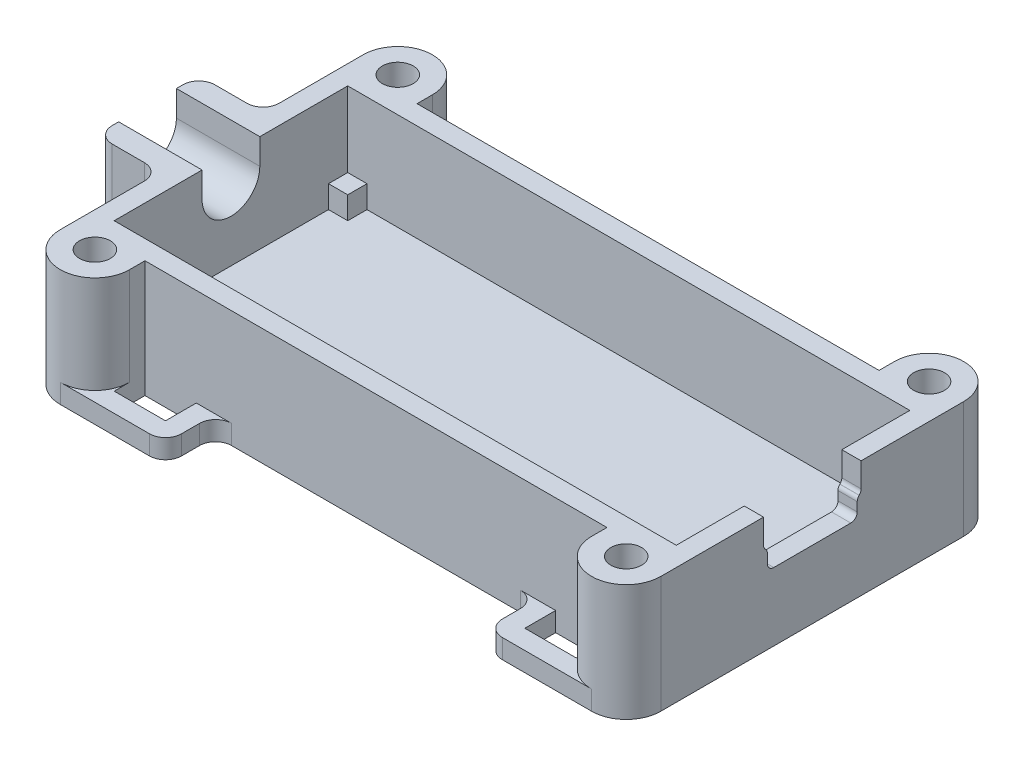
SolidWorks part; units mm, degrees
ref_plane "Front Plane" through (0, 0, 0) normal (0, 0, 1) x (1, 0, 0)
ref_plane "Top Plane" through (0, 0, 0) normal (0, 1, 0) x (1, 0, 0)
ref_plane "Right Plane" through (0, 0, 0) normal (1, 0, 0) x (0, 0, -1)
sketch "Sketch1" plane through (0, 0, 0) normal (0, 1, 0) x (1, 0, 0)
  line L0 (-21.9, 9.1) -> (-23.4, 9.1) construction
  line L1 (-21.9, 9.1) -> (21.9, 9.1)
  line L2 (-21.9, 9.1) -> (-21.9, -9.1)
  line L3 (-21.9, -9.1) -> (21.9, -9.1)
  line L4 (21.9, 9.1) -> (21.9, -9.1)
  line L5 (-21.9, 9.1) -> (21.9, -9.1) construction
  line L6 (-21.9, -9.1) -> (21.9, 9.1) construction
  line L7 (23.4, -10.6) -> (-23.4, -10.6)
  line L8 (23.4, -10.6) -> (23.4, 10.6)
  line L9 (23.4, 10.6) -> (-23.4, 10.6)
  line L10 (-23.4, -10.6) -> (-23.4, 10.6)
  line L11 (23.4, -10.6) -> (-23.4, 10.6) construction
  line L12 (23.4, 10.6) -> (-23.4, -10.6) construction
  line L13 (-21.9, 9.1) -> (-21.9, 10.6) construction
  line L14 (-19.5, 11.8) -> (-18, 11.8) construction
  line L15 (-23.4, 11.8) -> (-23.4, 10.6)
  line L16 (0, 30.5142) -> (0, -27.0472) construction
  line L17 (-40.1948, 0) -> (31.8876, 0) construction
  line L18 (-18, 11.8) -> (-18, 10.6)
  line L19 (18, 11.8) -> (18, 10.6)
  line L20 (23.4, 11.8) -> (23.4, 10.6)
  line L21 (23.4, -11.8) -> (23.4, -10.6)
  line L22 (18, -11.8) -> (18, -10.6)
  line L23 (-18, -11.8) -> (-18, -10.6)
  line L24 (-23.4, -11.8) -> (-23.4, -10.6)
  line L26 (-28.4, 4) -> (-23.4, 4)
  line L27 (-28.4, 4) -> (-28.4, -4)
  line L28 (-28.4, -4) -> (-23.4, -4)
  line L29 (-23.4, 4) -> (-23.4, -4)
  line L30 (-28.4, 4) -> (-23.4, -4) construction
  line L31 (-28.4, -4) -> (-23.4, 4) construction
  circle A0 centre (-20.7, 11.8) radius 1.2
  circle A1 centre (-20.7, 11.8) radius 2.7
  circle A2 centre (20.7, 11.8) radius 1.2
  circle A3 centre (20.7, 11.8) radius 2.7
  circle A4 centre (20.7, -11.8) radius 1.2
  circle A5 centre (20.7, -11.8) radius 2.7
  circle A6 centre (-20.7, -11.8) radius 1.2
  circle A7 centre (-20.7, -11.8) radius 2.7
  point P0 (0, 0)
  point P6 (0, 0)
  point P42 (-25.9, 0)
  dimension "D4" = 2.4
  dimension "D5" = 5
  dimension "D1" = 18.2
  dimension "D2" = 43.8
  dimension "D3" = 1.5
  dimension "D6" = 8
extrude "Boss-Extrude1" add sketch "Sketch1" along normal blind 7.6 contours A1 L9 L18 | L9 A1 A0 | A1 L15 L9 | L9 A3 L19 | A3 L9 A2 | L20 A3 L9 | A5 L7 L22 | A5 L7 A4 | A5 L21 L7 | L24 A7 L7 | A7 L7 A6 | L7 A7 L23 | L7 A7 L3 L2 L1 A1 L9 L10 | A7 L7 | L3 A7 L7 A5 | L7 A5 | A5 L7 L8 L9 A3 L1 L4 L3 | A3 L9 | L1 A3 L9 A1 | A1 L9 | L27 L28 L10 L26 region at (-22.6604, 0, 0) region at (0, 0, -9.8379) region at (-20.7, 0, -9.9829) region at (22.6604, 0, 0) region at (20.7, 0, -9.9829) region at (-23.2639, 0, -11.1989) region at (-23.3164, 0, -10.8968) region at (-18.0836, 0, -10.8968) region at (0, 0, 9.8379) region at (-20.7, 0, 9.9829) region at (18.1361, 0, -11.1989) region at (18.0836, 0, -10.8968) region at (23.3164, 0, -10.8968) region at (20.7, 0, 9.9829) region at (-18.1361, 0, 11.1989) region at (-18.0836, 0, 10.8968) region at (-23.3164, 0, 10.8968) region at (-25.9, 0, 0) region at (23.2639, 0, 11.1989) region at (23.3164, 0, 10.8968) region at (18.0836, 0, 10.8968)
sketch "Sketch3" plane through (0, 0, 0) normal (0, -1, 0) x (1, 0, 0)
  line L8 (-23.4, -4) -> (-23.4, -11.8)
  line L9 (-18, -11.8) -> (-18, -10.6)
  line L10 (-18, -10.6) -> (18, -10.6)
  line L11 (18, -10.6) -> (18, -11.8)
  line L12 (23.4, -11.8) -> (23.4, 11.8)
  line L13 (18, 11.8) -> (18, 10.6)
  line L14 (18, 10.6) -> (-18, 10.6)
  line L15 (-18, 10.6) -> (-18, 11.8)
  line L16 (-23.4, -4) -> (-23.4, -11.8)
  line L17 (-18, -11.8) -> (-18, -10.6)
  line L18 (-18, -10.6) -> (18, -10.6)
  line L19 (18, -10.6) -> (18, -11.8)
  line L20 (23.4, -11.8) -> (23.4, 11.8)
  line L21 (18, 11.8) -> (18, 10.6)
  line L22 (18, 10.6) -> (-18, 10.6)
  line L23 (-18, 10.6) -> (-18, 11.8)
  line L28 (-23.4, 11.8) -> (-23.4, 4)
  line L29 (-23.4, 11.8) -> (-23.4, 4)
  line L30 (-23.4, 4) -> (-28.4, 4)
  line L31 (-23.4, 4) -> (-28.4, 4)
  line L32 (-28.4, 4) -> (-28.4, -4)
  line L33 (-28.4, 4) -> (-28.4, -4)
  line L34 (-28.4, -4) -> (-23.4, -4)
  line L35 (-28.4, -4) -> (-23.4, -4)
  circle A0 centre (-20.7, -11.8) radius 1.2 construction
  circle A1 centre (20.7, -11.8) radius 1.2 construction
  circle A2 centre (20.7, 11.8) radius 1.2 construction
  circle A3 centre (-20.7, 11.8) radius 1.2 construction
  arc A4 (-18, 11.8) -> (-23.4, 11.8) centre (-20.7, 11.8) ccw
  arc A5 (-23.4, -11.8) -> (-18, -11.8) centre (-20.7, -11.8) ccw
  arc A6 (18, -11.8) -> (23.4, -11.8) centre (20.7, -11.8) ccw
  arc A7 (23.4, 11.8) -> (18, 11.8) centre (20.7, 11.8) ccw
  arc A8 (-18, 11.8) -> (-23.4, 11.8) centre (-20.7, 11.8) ccw
  arc A9 (-23.4, -11.8) -> (-18, -11.8) centre (-20.7, -11.8) ccw
  arc A10 (18, -11.8) -> (23.4, -11.8) centre (20.7, -11.8) ccw
  arc A11 (23.4, 11.8) -> (18, 11.8) centre (20.7, 11.8) ccw
  circle A12 centre (-20.7, -11.8) radius 1.2
  circle A13 centre (20.7, -11.8) radius 1.2
  circle A14 centre (20.7, 11.8) radius 1.2
  circle A15 centre (-20.7, 11.8) radius 1.2
  dimension "D1" = 0
extrude "Boss-Extrude2" add sketch "Sketch3" along normal blind 1.5
sketch "Sketch4" plane through (-28.4, 0, 0) normal (-1, 0, 0) x (0, 0, 1)
  line L0 (-9.1, 0) -> (9.1, 0) construction
  line L1 (-9.1, 0) -> (9.1, 0)
  line L2 (0, 7.6) -> (0, -1.5) construction
  line L3 (-4, 7.6) -> (-11.8, 7.6) construction
  line L5 (0, 3.35) -> (11.8, 3.35) construction
  line L6 (11.8, 7.6) -> (11.8, -1.5) construction
  line L7 (-2.25, 5.6) -> (-2.25, 7.6)
  line L8 (2.25, 5.6) -> (2.25, 7.6)
  line L9 (-2.25, 7.6) -> (2.25, 7.6)
  line L11 (-4, 7.6) -> (4, 7.6) construction
  line L12 (4, -1.5) -> (-4, -1.5) construction
  circle A0 centre (0, 5.6) radius 2.25
  line M23 (4, 7.6) -> (-4, 7.6)
  dimension "D2" = 4.5
  dimension "D1" = 3.35
extrude "Cut-Extrude1" cut sketch "Sketch4" against normal up to next contours A0 L8 L7 | A0 | A0 L7 M23 region at (-28.4, 5.5531, 0) region at (-28.4, 7.131, -1.911) region at (-28.4, 7.131, 1.911)
sketch "Sketch5" plane through (0, 0, 0) normal (0, 1, 0) x (1, 0, 0)
  line L0 (0, 18.1559) -> (0, -18.574) construction
  line L1 (-21.9, 9.1) -> (-20.4, 9.1)
  line L2 (-21.9, 9.1) -> (-21.9, 7.6)
  line L3 (-21.9, 7.6) -> (-20.4, 7.6)
  line L4 (-20.4, 9.1) -> (-20.4, 7.6)
  line L5 (-28.7323, 0) -> (29.8474, 0) construction
  line L6 (21.9, 9.1) -> (21.9, 7.6)
  line L7 (21.9, 9.1) -> (20.4, 9.1)
  line L8 (20.4, 9.1) -> (20.4, 7.6)
  line L9 (21.9, 7.6) -> (20.4, 7.6)
  line L10 (-21.9, -9.1) -> (-21.9, -7.6)
  line L11 (-21.9, -9.1) -> (-20.4, -9.1)
  line L12 (-20.4, -9.1) -> (-20.4, -7.6)
  line L13 (-21.9, -7.6) -> (-20.4, -7.6)
  line L14 (21.9, -9.1) -> (21.9, -7.6)
  line L15 (21.9, -9.1) -> (20.4, -9.1)
  line L16 (20.4, -9.1) -> (20.4, -7.6)
  line L17 (21.9, -7.6) -> (20.4, -7.6)
  dimension "D1" = 1.5
extrude "Boss-Extrude3" add sketch "Sketch5" along normal blind 1.75
sketch "Sketch6" plane through (23.4, 0, 0) normal (1, 0, 0) x (0, 0, -1)
  line L1 (0, 7.6) -> (0, -1.5) construction
  line L2 (11.8, 7.6) -> (-11.8, 7.6) construction
  line L3 (11.8, -1.5) -> (-11.8, -1.5) construction
  line L4 (7.6, 0) -> (-7.6, 0) construction
  line L5 (7.6, 0) -> (-7.6, 0)
  line L6 (-3.8, 5.2) -> (3.8, 5.2) construction
  line L7 (-3.8, 7.6) -> (3.8, 7.6)
  line L8 (-3.8, 7.6) -> (-3.8, 3.8)
  line L9 (-3.8, 3.8) -> (3.8, 3.8)
  line L10 (3.8, 7.6) -> (3.8, 3.8)
  line L11 (-3.8, 7.6) -> (3.8, 3.8) construction
  line L12 (-3.8, 3.8) -> (3.8, 7.6) construction
  line L13 (-3.5, 5.2) -> (-3.5, 3.8)
  line L14 (-3.5, 5.2) -> (-3.8, 5.5)
  line L15 (3.5, 5.2) -> (3.5, 3.8)
  line L16 (3.5, 5.2) -> (3.8, 5.5)
  point P8 (0, 5.7)
  line M9 (11.8, 7.6) -> (-11.8, 7.6)
  dimension "D1" = 3.8
  dimension "D2" = 7.6
  dimension "D3" = 1.4
  dimension "D4" = 7
  dimension "D5" = 45
extrude "Cut-Extrude2" cut sketch "Sketch6" against normal up to next contours L10 L8 L9 M9 region at (23.4, 5.7374, 0)
sketch "Sketch8" plane through (0, -1.5, 0) normal (0, -1, 0) x (1, 0, 0)
  line L0 (-20.7, 14.5) -> (-12.5, 14.5)
  line L1 (-18, 10.6) -> (-14, 10.6)
  line L2 (-18, 10.6) -> (-18, 13)
  line L3 (-18, 13) -> (-14, 13)
  line L4 (-14, 10.6) -> (-14, 13)
  line L5 (-12.5, 14.5) -> (-12.5, 10.6)
  line L6 (18, 10.6) -> (-18, 10.6) construction
  line L7 (-14, 13) -> (-14, 14.5) construction
  line L8 (-14, 13) -> (-12.5, 13) construction
  line L9 (0, 29.3193) -> (0, -24.0926) construction
  line L10 (-37.5157, 0) -> (37.6606, 0) construction
  line L11 (18, 10.6) -> (14, 10.6)
  line L12 (18, 10.6) -> (18, 13)
  line L13 (18, 13) -> (14, 13)
  line L14 (14, 10.6) -> (14, 13)
  line L15 (12.5, 14.5) -> (12.5, 10.6)
  line L16 (20.7, 14.5) -> (12.5, 14.5)
  line L17 (-12.5, -14.5) -> (-12.5, -10.6)
  line L18 (-20.7, -14.5) -> (-12.5, -14.5)
  line L19 (-18, -10.6) -> (-14, -10.6)
  line L20 (-18, -10.6) -> (-18, -13)
  line L21 (-18, -13) -> (-14, -13)
  line L22 (-14, -10.6) -> (-14, -13)
  line L23 (20.7, -14.5) -> (12.5, -14.5)
  line L24 (12.5, -14.5) -> (12.5, -10.6)
  line L25 (14, -10.6) -> (14, -13)
  line L26 (18, -13) -> (14, -13)
  line L27 (18, -10.6) -> (18, -13)
  line L28 (18, -10.6) -> (14, -10.6)
  arc A0 (-18, 11.8) -> (-23.4, 11.8) centre (-20.7, 11.8) ccw construction
  arc M20 (-23.4, -11.8) -> (-18, -11.8) centre (-20.7, -11.8) ccw
  line M22 (-18, -10.6) -> (18, -10.6)
  arc M24 (18, -11.8) -> (23.4, -11.8) centre (20.7, -11.8) ccw
  arc M26 (23.4, 11.8) -> (18, 11.8) centre (20.7, 11.8) ccw
  line M28 (18, 10.6) -> (-18, 10.6)
  arc M30 (-18, 11.8) -> (-23.4, 11.8) centre (-20.7, 11.8) ccw
  dimension "D1" = 2.4
  dimension "D2" = 4
extrude "Boss-Extrude4" add sketch "Sketch8" against normal blind 1.5 contours L5 L0 L2 L3 L4 M30 M28 | L16 L15 L14 L13 L12 M26 M28 | L27 L26 L25 L24 L23 M24 M22 | L22 L21 L20 L18 L17 M22 M20 region at (15.1043, -1.5, 13.2438) region at (-15.1043, -1.5, 13.2438) region at (-15.1043, -1.5, -13.2438) region at (15.1043, -1.5, -13.2438)
fillet "Fillet1" radius 1.25 12 edges at (-28.4, 3.05, 4) (-28.4, 3.05, -4) (-23.4, 3.05, -4) (-23.4, 3.05, 4) (-12.5, -0.75, -10.6) (-12.5, -0.75, -14.5) (12.5, -0.75, -14.5) (12.5, -0.75, -10.6) (12.5, -0.75, 14.5) (12.5, -0.75, 10.6) (-12.5, -0.75, 10.6) (-12.5, -0.75, 14.5)
fillet "Fillet2" radius 0.5 6 edges at (22.65, 3.8, 3.5) (22.65, 3.8, -3.5) (22.65, 5.2, -3.5) (22.65, 5.5, -3.8) (22.65, 5.2, 3.5) (22.65, 5.5, 3.8)
